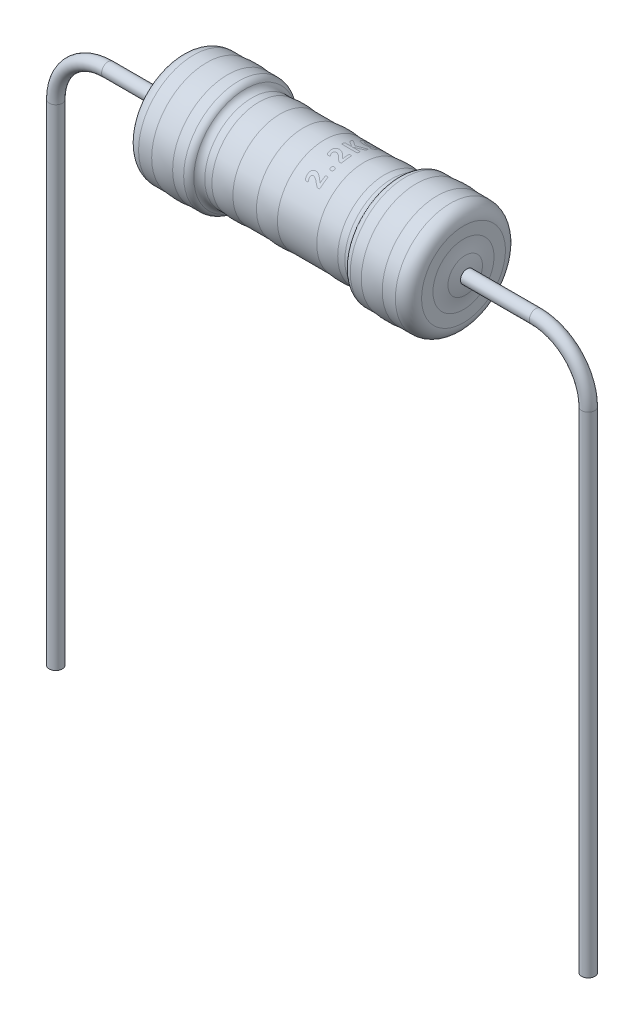
SolidWorks part; units mm, degrees
ref_plane "Front Plane" through (0, 0, 0) normal (0, 0, 1) x (1, 0, 0)
ref_plane "Top Plane" through (0, 0, 0) normal (0, 1, 0) x (1, 0, 0)
ref_plane "Right Plane" through (0, 0, 0) normal (1, 0, 0) x (0, 0, -1)
sketch "Sketch Set Wire Width" plane through (0, 0, 0) normal (0, 0, 1) x (1, 0, 0)
  line L0 (-8.16, 0) -> (8.16, 0)
  line L1 (-10.16, -2) -> (-10.16, -20.6984)
  line L2 (10.16, -2) -> (10.16, -20.6984)
  line L3 (-10.16, -20.6984) -> (10.16, -20.6984) construction
  line L4 (0, 0) -> (0, -20.6984) construction
  arc A0 (-8.16, 0) -> (-10.16, -2) centre (-8.16, -2) ccw
  arc A1 (8.16, 0) -> (10.16, -2) centre (8.16, -2) cw
  dimension "D2" = 2
  dimension "D3" = 60
  dimension "D1" = 20.32
sketch "Sketch Wire Diameter" plane through (0, 0, 0) normal (1, 0, 0) x (0, 0, -1)
  circle A0 centre (0, 0) radius 0.25
  dimension "D1" = 0.5
sweep "SET WIRE LENGTH" add profiles "Sketch Wire Diameter" path "Sketch Set Wire Width"
sketch "Sketch3" plane through (0, 0, 0) normal (0, 0, 1) x (1, 0, 0)
  line L0 (-5.4, 0) -> (5.4, 0)
  line L1 (0, 0) -> (0, 1.8) construction
  line L2 (-2.9, 1.8) -> (2.9, 1.8)
  line L3 (-5.4, 0) -> (-5.4, 1.6)
  line L4 (-4.9, 2.1) -> (-3.18, 2.1)
  line L5 (-2.9, 1.82) -> (-2.9, 1.8)
  line L6 (5.4, 0) -> (5.4, 1.6)
  line L7 (4.9, 2.1) -> (3.18, 2.1)
  line L8 (2.9, 1.82) -> (2.9, 1.8)
  arc A0 (-5.4, 1.6) -> (-4.9, 2.1) centre (-4.9, 1.6) cw
  arc A1 (5.4, 1.6) -> (4.9, 2.1) centre (4.9, 1.6) ccw
  arc A2 (-3.18, 2.1) -> (-2.9, 1.82) centre (-3.18, 1.82) cw
  arc A3 (3.18, 2.1) -> (2.9, 1.82) centre (3.18, 1.82) ccw
  dimension "D5" = 0.5
  dimension "D6" = 0.28
  dimension "D1" = 10.8
  dimension "D2" = 5.8
  dimension "D3" = 1.8
  dimension "D4" = 2.1
revolve "Revolve2" add sketch "Sketch3" angle 360 about L0
fillet "Fillet1" radius 0.3 2 edges at (2.9, 0, 1.8) (-2.9, 0, 1.8)
sketch "Sketch5" plane through (0, 0, 0) normal (0, 0, 1) x (1, 0, 0)
  line L0 (0, 0) -> (2, 0) construction
  line L1 (0, 0) -> (-0.3, 0) construction
  line L2 (-0.3, 0) -> (-2, 0) construction
  line L3 (-2, 0) -> (-4, 0) construction
  line L4 (2, 0) -> (4, 0) construction
  line L5 (-4, 0) -> (-4, 2.1) construction
  line L6 (-0.3, 0) -> (-0.3, 1.8) construction
  line L7 (-2, 0) -> (-2, 1.8) construction
  line L8 (2, 0) -> (2, 1.8) construction
  line L9 (4, 0) -> (4, 2.1) construction
  line L10 (-4, 2.1) -> (-4, 2.13) construction
  line L11 (-4.9, 2.1) -> (-3.18, 2.1) construction
  line L12 (4.9, 2.1) -> (3.18, 2.1) construction
  line L13 (-2.9, 1.8) -> (2.9, 1.8) construction
  line L14 (-2, 1.8) -> (-2, 1.83) construction
  line L17 (-4.4, 2.1) -> (-3.6, 2.1)
  line L19 (-5.4, 0) -> (5.4, 0) construction
  line L22 (-2.4, 1.8) -> (-1.6, 1.8) construction
  line L26 (-0.7, 1.8) -> (0.1, 1.8) construction
  line L30 (1.6, 1.8) -> (2.4, 1.8) construction
  line L34 (3.6, 2.1) -> (4.4, 2.1) construction
  line L36 (-0.3, 1.8) -> (-0.3, 1.83) construction
  line L37 (2, 1.8) -> (2, 1.83) construction
  line L38 (4, 2.1) -> (4, 2.13) construction
  arc A0 (-4.4, 2.1) -> (-3.6, 2.1) centre (-4, -0.5517) cw
  arc A1 (-2.4, 1.8) -> (-1.6, 1.8) centre (-2, -0.8517) cw construction
  arc A2 (-0.7, 1.8) -> (0.1, 1.8) centre (-0.3, -0.8517) cw construction
  arc A3 (1.6, 1.8) -> (2.4, 1.8) centre (2, -0.8517) cw construction
  arc A4 (3.6, 2.1) -> (4.4, 2.1) centre (4, -0.5517) cw construction
  dimension "D3" = 0.8
  dimension "D1" = 4
  dimension "D2" = 4
  dimension "D4" = 0.03
  dimension "D5" = 2
  dimension "D6" = 2
  dimension "D7" = 1.7
revolve "Band 1" add sketch "Sketch5" angle 360 about L2
sketch "Sketch8" plane through (0, 0, 0) normal (0, 0, 1) x (1, 0, 0)
  line L0 (-2.4, 1.8) -> (-1.6, 1.8) construction
  line L1 (-2.4, 1.8) -> (-1.6, 1.8)
  arc A0 (-1.6, 1.8) -> (-2.4, 1.8) centre (-2, -0.8517) ccw construction
  arc A1 (-1.6, 1.8) -> (-2.4, 1.8) centre (-2, -0.8517) ccw
revolve "Band 2" add sketch "Sketch8" angle 360 about L2
sketch "Sketch9" plane through (0, 0, 0) normal (0, 0, 1) x (1, 0, 0)
  line L0 (-0.7, 1.8) -> (0.1, 1.8) construction
  line L1 (-0.7, 1.8) -> (0.1, 1.8)
  arc A0 (0.1, 1.8) -> (-0.7, 1.8) centre (-0.3, -0.8517) ccw construction
  arc A1 (0.1, 1.8) -> (-0.7, 1.8) centre (-0.3, -0.8517) ccw
revolve "Band 3" add sketch "Sketch9" angle 360 about L2
sketch "Sketch10" plane through (0, 0, 0) normal (0, 0, 1) x (1, 0, 0)
  line L0 (1.6, 1.8) -> (2.4, 1.8) construction
  line L1 (1.6, 1.8) -> (2.4, 1.8)
  arc A0 (2.4, 1.8) -> (1.6, 1.8) centre (2, -0.8517) ccw construction
  arc A1 (2.4, 1.8) -> (1.6, 1.8) centre (2, -0.8517) ccw
revolve "Band 4" add sketch "Sketch10" angle 360 about L0
sketch "Sketch11" plane through (0, 0, 0) normal (0, 0, 1) x (1, 0, 0)
  line L0 (3.6, 2.1) -> (4.4, 2.1) construction
  line L1 (3.6, 2.1) -> (4.4, 2.1)
  arc A0 (4.4, 2.1) -> (3.6, 2.1) centre (4, -0.5517) ccw construction
  arc A1 (4.4, 2.1) -> (3.6, 2.1) centre (4, -0.5517) ccw
revolve "Band 5" add sketch "Sketch11" angle 360 about L4
sketch "Sketch12" plane through (0, 0, 0) normal (0, 0, 1) x (1, 0, 0)
  line L0 (-5.35, 0) -> (5.35, 0) construction
  line L1 (-5.35, 1) -> (-5.35, 0)
  line L2 (5.35, 1) -> (5.35, 0)
  line L3 (-5.35, 0) -> (-5.55, 0)
  line L4 (5.35, 0) -> (5.55, 0)
  arc A0 (-5.35, 1) -> (-5.55, 0) centre (-2.95, 0) ccw
  arc A1 (5.35, 1) -> (5.55, 0) centre (2.95, 0) cw
  dimension "D3" = 0.2
  dimension "D4" = 2.6
  dimension "D1" = 10.7
  dimension "D2" = 1
revolve "Revolve10" add sketch "Sketch12" angle 360 about L0
fillet "Fillet2" radius 2 2 edges at (5.4, 0, 0.8703) (-5.4, 0, -0.8703)
ref_plane "Plane2" through (0, 3, 0) normal (0, 1, 0) x (1, 0, 0)
sketch "Sketch13" plane through (0, 3, 0) normal (0, 1, 0) x (1, 0, 0)
  line L0 (0, 0) -> (1.15, 0) construction
  line L1 (1.15, 1.75) -> (1.15, -1.75) construction
  text T0 "2.2KΩ" font "Calibri" height 0.6
  dimension "D1" = 3.5
  dimension "D2" = 1.15
wrap "Wrap1" sketch "Sketch13" wrap type scribe source sketch "Sketch13" face at (0.1, 1.8, 0)
